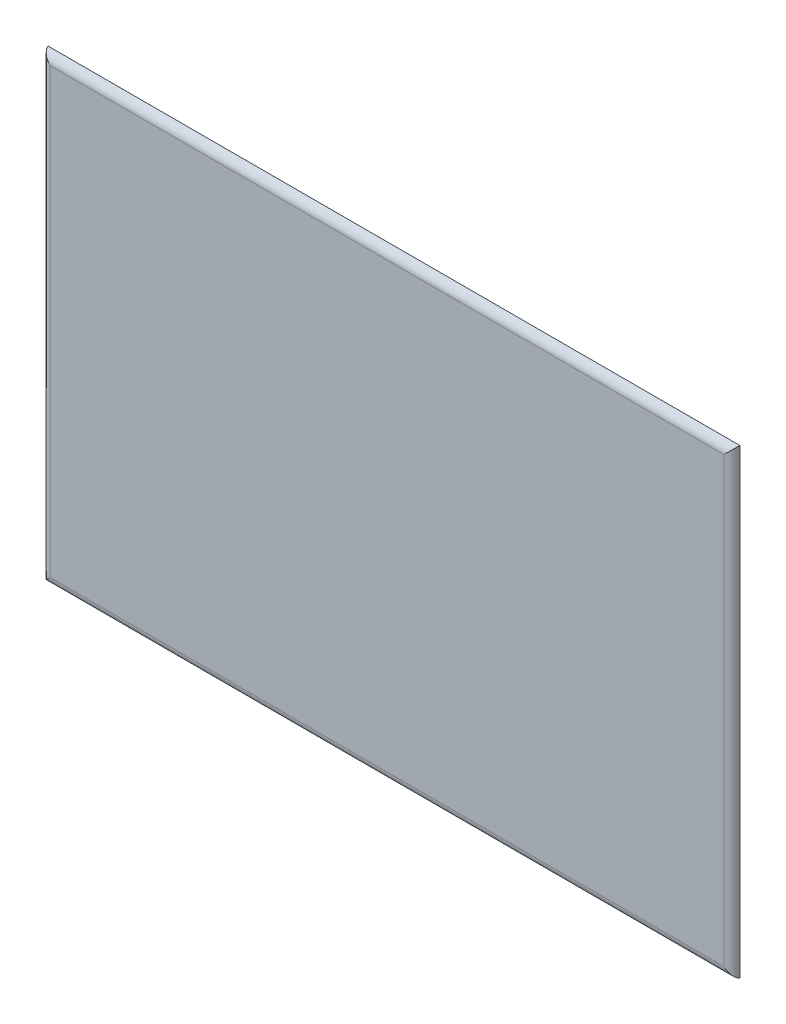
SolidWorks part; units mm, degrees
ref_plane "Front Plane" through (0, 0, 0) normal (0, 0, 1) x (1, 0, 0)
ref_plane "Top Plane" through (0, 0, 0) normal (0, 1, 0) x (1, 0, 0)
ref_plane "Right Plane" through (0, 0, 0) normal (1, 0, 0) x (0, 0, -1)
sketch "Sketch1" plane through (0, 0, 0) normal (0, 0, 1) x (1, 0, 0)
  line L1 (-48.7738, 17.025) -> (251.2262, 17.025)
  line L2 (-48.7738, 17.025) -> (-48.7738, -182.975)
  line L3 (-48.7738, -182.975) -> (251.2262, -182.975)
  line L4 (251.2262, 17.025) -> (251.2262, -182.975)
extrude "Boss-Extrude1" add sketch "Sketch1" along normal blind 3
fillet "Fillet1" radius 4 4 edges at (101.2262, -182.975, 3) (-48.7738, -82.975, 3) (251.2262, -82.975, 3) (101.2262, 17.025, 3)
sketch "Sketch2" plane through (0, 0, 0) normal (0, 0, 1) x (1, 0, 0)
  line L0 (-44.9009, -41.5109) -> (247.3532, -41.5109) construction
  line L1 (-44.9009, 13.1521) -> (-44.9009, -179.102) construction
  line L2 (247.3532, -179.102) -> (247.3532, 13.1521) construction
  line L3 (-44.9009, -94.1438) -> (247.3532, -94.1438) construction
  line L4 (-44.9009, -138.5678) -> (247.3532, -138.5678) construction
  circle A0 centre (0, -16.4017) radius 10
  circle A1 centre (40, -16.4017) radius 10
  circle A2 centre (80, -16.4017) radius 10
  circle A3 centre (120, -16.4017) radius 10
  circle A4 centre (160, -16.4017) radius 10
  circle A5 centre (200, -16.4017) radius 10
  circle A6 centre (200, -66.6202) radius 10
  circle A7 centre (160, -66.6202) radius 10
  circle A8 centre (120, -66.6202) radius 10
  circle A9 centre (80, -66.6202) radius 10
  circle A10 centre (40, -66.6202) radius 10
  circle A11 centre (0, -66.6202) radius 10
  circle A12 centre (200, -121.6673) radius 10
  circle A13 centre (160, -121.6673) radius 10
  circle A14 centre (120, -121.6673) radius 10
  circle A15 centre (80, -121.6673) radius 10
  circle A16 centre (40, -121.6673) radius 10
  circle A17 centre (0, -121.6673) radius 10
  circle A18 centre (200, -155.4682) radius 10
  circle A19 centre (160, -155.4682) radius 10
  circle A20 centre (120, -155.4682) radius 10
  circle A21 centre (80, -155.4682) radius 10
  circle A22 centre (40, -155.4682) radius 10
  circle A23 centre (0, -155.4682) radius 10
  dimension "D1" = 6
extrude "Boss-Extrude3" add sketch "Sketch2" against normal blind 7
